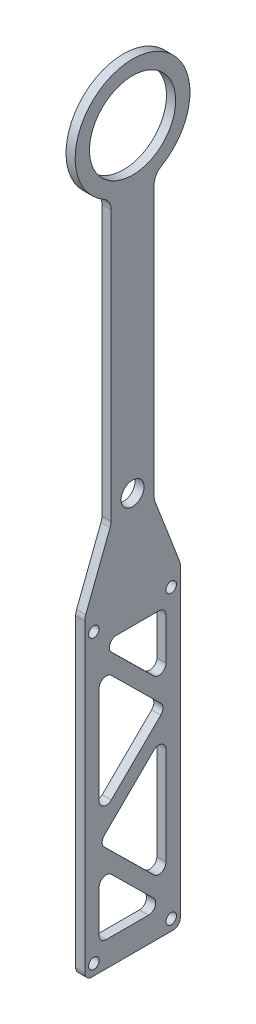
SolidWorks part; units mm, degrees
material "6061 Alloy"
ref_plane "Front Plane" through (0, 0, 0) normal (0, 0, 1) x (1, 0, 0)
ref_plane "Top Plane" through (0, 0, 0) normal (0, 1, 0) x (1, 0, 0)
ref_plane "Right Plane" through (0, 0, 0) normal (1, 0, 0) x (0, 0, -1)
sketch "Sketch1" plane through (0, 0, 0) normal (1, 0, 0) x (0, 0, -1)
  line L0 (-13.4747, 0) -> (13.4747, 0) construction
  line L1 (0, 0) -> (0, 35) construction
  line L2 (-13.4747, 0) -> (0, 35) construction
  line L3 (0, 35) -> (13.4747, 0) construction
  line L4 (13.4747, 0) -> (-13.4747, 0) construction
  line L5 (20.7574, -5) -> (-20.7574, -5)
  line L6 (-20.7574, -5) -> (0, 48.9165)
  line L7 (0, 48.9165) -> (20.7574, -5)
  line L8 (0, 35) -> (0, 146) construction
  line L9 (0, 35) -> (0, 146) construction
  line L12 (-7.5, 35) -> (-7.5, 146)
  line L13 (7.5, 35) -> (7.5, 146)
  line L14 (-7.5, 35) -> (-7.5, 29.4356)
  line L15 (7.5, 35) -> (7.5, 29.4356)
  line L16 (-13.4747, 0) -> (13.4747, 0) construction
  line L17 (-13.4747, 0) -> (-13.4747, -100) construction
  line L18 (13.4747, 0) -> (13.4747, -100) construction
  line L19 (-13.4747, -100) -> (13.4747, -100) construction
  line L20 (-20.7574, -5) -> (20.7574, -5)
  line L21 (-20.7574, -5) -> (-20.7574, -103.81)
  line L22 (20.7574, -5) -> (20.7574, -103.81)
  line L23 (-20.7574, -103.81) -> (20.7574, -103.81)
  circle A0 centre (-13.4747, 0) radius 1.8288
  circle A1 centre (0, 35) radius 4
  circle A2 centre (13.4747, 0) radius 1.8288
  circle A3 centre (0, 146) radius 3 construction
  arc A6 (-7.5, 35) -> (7.5, 35) centre (0, 35) ccw
  arc A7 (7.5, 146) -> (-7.5, 146) centre (0, 146) ccw
  circle A8 centre (-13.4747, -100) radius 1.8288
  circle A9 centre (13.4747, -100) radius 1.8288
  circle A17 centre (0, 146) radius 15
  circle A18 centre (0, 146) radius 20
  point P4 (0, 0)
  point P14 (0, 90.5)
  point P34 (0, 146)
  dimension "D3" = 3.6576
  dimension "D4" = 8
  dimension "D7" = 6
  dimension "D13" = 30
  dimension "D14" = 40
  dimension "D1" = 26.9494
  dimension "D5" = 111
  dimension "D6" = 15
  dimension "D8" = 100
  dimension "D9" = 3.81
  dimension "D10" = 35
  dimension "D2" = 5
extrude "Boss-Extrude1" add sketch "Sketch1" along normal blind 3.175 contours L13 A18 L12 A17 | L12 A18 L13 A17 | A18 L12 A6 L6 L7 L13 | L6 A6 L7 A1 | A6 L6 L5 L7 A2 A0 | A6 L14 L6 | A6 L7 L15 | L21 L23 L22 L5 A9 A8 region at (0, -54.1702, 0) region at (0, 9.5725, 0) region at (0, 31.6598, -7.2402) region at (0, 31.6598, 7.2402) region at (0, 27.7524, 0) region at (0, 82.7884, 0) region at (0, 129.0809, 0) region at (0, 130.2346, -8.0555)
sketch "Sketch2" plane through (3.175, 0, 0) normal (1, 0, 0) x (0, 0, -1)
  line L0 (-11.645, -5) -> (11.645, -5) construction
  line L1 (-11.645, -95) -> (11.645, -95) construction
  line L2 (11.645, -95) -> (11.645, -5) construction
  line L3 (-11.645, -95) -> (-11.645, -5) construction
  line L6 (11.645, -38.5118) -> (-11.645, -61.4882) construction
  line L7 (11.645, -5) -> (-11.645, -5)
  line L8 (-11.645, -5) -> (11.645, -27.9764)
  line L9 (11.645, -27.9764) -> (11.645, -5)
  line L10 (-11.645, -12.0236) -> (11.645, -35)
  line L11 (11.645, -35) -> (-11.645, -57.9764)
  line L12 (-11.645, -57.9764) -> (-11.645, -35)
  line L13 (-11.645, -35) -> (-11.645, -12.0236)
  line L14 (-11.645, -72.0236) -> (-11.645, -95)
  line L15 (-11.645, -95) -> (11.645, -95)
  line L16 (11.645, -95) -> (-11.645, -72.0236)
  line L17 (11.645, -42.0236) -> (11.645, -65)
  line L18 (11.645, -65) -> (11.645, -87.9764)
  line L19 (11.645, -87.9764) -> (-11.645, -65)
  line L20 (-11.645, -65) -> (11.645, -42.0236)
  line L21 (16.645, -1056.0877) -> (16.645, 48943.9123) construction
  line L22 (-16.645, -1060.2922) -> (-16.645, 48939.7078) construction
  line L23 (16.645, 29.4356) -> (-16.645, 29.4356) construction
  line L24 (-20.7574, -103.81) -> (-16.645, -103.81)
  line L25 (-20.7574, -103.81) -> (-20.7574, 29.4356)
  line L26 (-16.645, -103.81) -> (-16.645, 29.4356)
  line L27 (-20.7574, 29.4356) -> (-16.645, 29.4356)
  line L28 (-20.7574, -103.81) -> (20.7574, -103.81) construction
  line L29 (20.7574, -103.81) -> (16.645, -103.81)
  line L30 (20.7574, -103.81) -> (20.7574, 29.4356)
  line L31 (16.645, -103.81) -> (16.645, 29.4356)
  line L32 (20.7574, 29.4356) -> (16.645, 29.4356)
  circle A0 centre (13.4747, 0) radius 1.8288 construction
  circle A1 centre (13.4747, -100) radius 1.8288 construction
  point P6 (11.645, -50)
  point P10 (0, 29.4356)
  point P21 (0, -50)
  dimension "D1" = 33.29
  dimension "D2" = 5
  dimension "D3" = 5
  dimension "D4" = 5
  dimension "D5" = 5
  dimension "D6" = 2.5
  dimension "D8" = 5
  dimension "D7" = 2
extrude "Cut-Extrude1" cut sketch "Sketch2" against normal up to next
fillet "Fillet3" radius 2.5 14 edges at (1.5875, -57.9764, 11.645) (1.5875, -35, -11.645) (1.5875, -95, -11.645) (1.5875, -72.0236, 11.645) (1.5875, -95, 11.645) (1.5875, -27.9764, -11.645) (1.5875, -5, -11.645) (1.5875, -12.0236, 11.645) (1.5875, -5, 11.645) (1.5875, -87.9764, -11.645) (1.5875, -42.0236, -11.645) (1.5875, -65, 11.645) (1.5875, -103.81, -16.645) (1.5875, -103.81, 16.645)
fillet "Fillet4" radius 5 6 edges at (1.5875, 29.4356, -7.5) (1.5875, 29.4356, 7.5) (1.5875, 5.6818, 16.645) (1.5875, 5.6818, -16.645) (1.5875, 127.4595, -7.5) (1.5875, 127.4595, 7.5)
